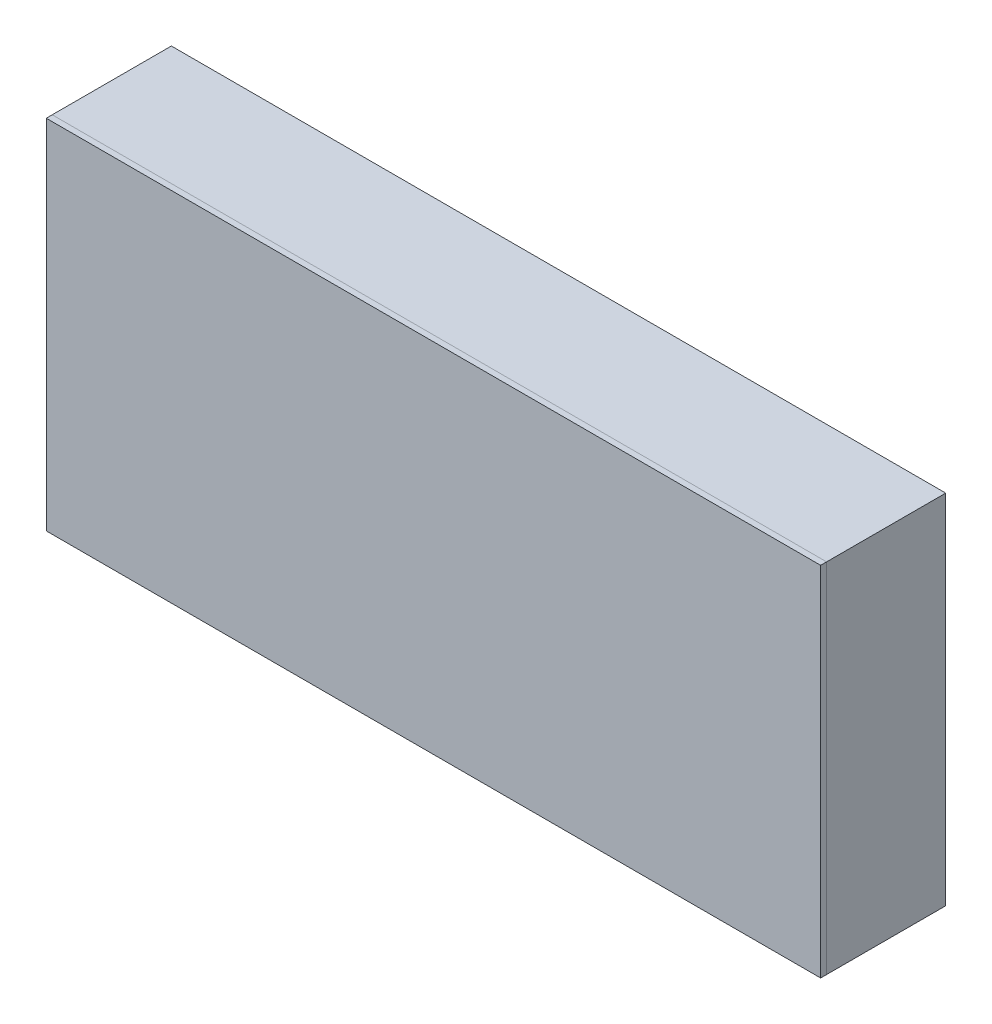
SolidWorks part; units mm, degrees
note: The reader was unsure of these and kept them because the rebuilt part matched: shared geometry of "Sketch1<2>", "Sketch4<4>".
ref_plane "Front Plane" through (0, 0, 0) normal (0, 0, 1) x (1, 0, 0)
ref_plane "Top Plane" through (0, 0, 0) normal (0, 1, 0) x (1, 0, 0)
ref_plane "Right Plane" through (0, 0, 0) normal (1, 0, 0) x (0, 0, -1)
sketch "Sketch1" plane through (0, 0, 0) normal (0, 0, 1) x (1, 0, 0)
  line L0 (-65, 30) -> (-65, 8.0004)
  line L1 (65, -30) -> (-65, -30)
  line L2 (65, -30) -> (65, 30)
  line L3 (65, 30) -> (-65, 30)
  line L4 (-65, -30) -> (-65, -8.9996)
  line L5 (65, -30) -> (-65, 30) construction
  line L6 (65, 30) -> (-65, -30) construction
  point P0 (0, 0)
  dimension "D1" = 130
  dimension "D2" = 60
  dimension "D3" = 17
extrude "Extrude-Thin1" add sketch "Sketch1" along normal blind 20 thin thin type one direction wall 2
extrude "Extrude-Thin2" add sketch "Sketch1<2>" along normal blind 1 thin thin type one direction wall 12
sketch "Sketch1<2>" plane through (0, 0, 0) normal (0, 0, 1) x (1, 0, 0) same geometry as "Sketch1"
ref_plane "Plane1" through (0, 0, 14) normal (0, 0, 1) x (1, 0, 0)
sketch "Sketch2" plane through (0, 0, 14) normal (0, 0, 1) x (1, 0, 0)
  line L0 (-65, 30) -> (-65, 8.0004) construction
  line L1 (65, 30) -> (-65, 30) construction
  line L2 (65, -30) -> (65, 30) construction
  line L3 (65, -30) -> (-65, -30) construction
  line L4 (-65, -30) -> (-65, -8.9996) construction
  line L5 (-65, 30) -> (-65, 8.0004) construction
  line L6 (65, 30) -> (-65, 30) construction
  line L7 (65, -30) -> (65, 30) construction
  line L8 (65, -30) -> (-65, -30) construction
  line L9 (-65, -30) -> (-65, -8.9996) construction
  line L10 (-65, 8.0004) -> (-65, -8.9996)
extrude "Extrude-Thin3" add sketch "Sketch2" along normal blind 6 separate body thin thin type one direction reverse wall 2
sketch "Sketch3" plane through (-63, 0, 0) normal (1, 0, 0) x (0, 0, -1)
  line L0 (-14, 8.0004) -> (-14, -8.9996) construction
  line L1 (-14, -6.9996) -> (-12, -8.9996)
  line L2 (-20, -8.9996) -> (-1, -8.9996) construction
  line L3 (-14, 6.0004) -> (-12, 8.0004)
  line L4 (-20, 8.0004) -> (-1, 8.0004) construction
  line L5 (-14, -6.9996) -> (-14, -8.9996)
  line L6 (-14, -8.9996) -> (-12, -8.9996)
  line L7 (-14, 6.0004) -> (-14, 8.0004)
  line L8 (-14, 8.0004) -> (-12, 8.0004)
  dimension "D1" = 135
  dimension "D2" = 45
  dimension "D3" = 12
  dimension "D4" = 12
extrude "Boss-Extrude1" add sketch "Sketch3" against normal blind 2
sketch "Sketch4" plane through (0, 0, 20) normal (0, 0, 1) x (1, 0, 0)
  line L0 (-65, 30) -> (65, 30) construction
  line L1 (-65, -30) -> (-65, 30) construction
  line L2 (65, -30) -> (-65, -30) construction
  line L3 (65, 30) -> (65, -30) construction
  line L4 (-65, 30) -> (65, 30)
  line L5 (-65, -30) -> (-65, 30)
  line L6 (65, -30) -> (-65, -30)
  line L7 (65, 30) -> (65, -30)
  line L8 (-63, 28) -> (63, 28) construction
  line L9 (-63, -28) -> (-63, 28) construction
  line L10 (63, -28) -> (-63, -28) construction
  line L11 (63, 28) -> (63, -28) construction
  line L12 (-63, 28) -> (63, 28) construction
  line L13 (-63, -28) -> (-63, 28) construction
  line L14 (63, -28) -> (-63, -28) construction
  line L15 (63, 28) -> (63, -28) construction
  line L16 (62.75, 27.75) -> (62.75, -27.75)
  line L17 (62.75, -27.75) -> (-62.75, -27.75)
  line L18 (-62.75, -27.75) -> (-62.75, 27.75)
  line L19 (-62.75, 27.75) -> (62.75, 27.75)
  line M2 (-63, 28) -> (63, 28)
  line M3 (63, 28) -> (63, -28)
  line M4 (63, -28) -> (-63, -28)
  line M5 (65, 30) -> (-65, 30)
  line M7 (-65, -30) -> (65, -30)
  line M8 (65, -30) -> (65, 30)
  line M13 (-63, -28) -> (-63, 28)
  line M15 (-65, 30) -> (-65, -30)
  dimension "D1" = 0.25
extrude "Boss-Extrude2" add sketch "Sketch4" along normal blind 1 separate body contours M8 M5 M15 M7 M4 M13 M2 M3 | L18 L19 L16 L17 M13 M4 M3 M2 | L19 L18 L17 L16 | L4 L7 L6 L5
extrude "Extrude-Thin4" add sketch "Sketch4<4>" against normal blind 5 thin contours L16 L17 L18 L19
sketch "Sketch4<4>" plane through (0, 0, 20) normal (0, 0, 1) x (1, 0, 0) same geometry as "Sketch4"
